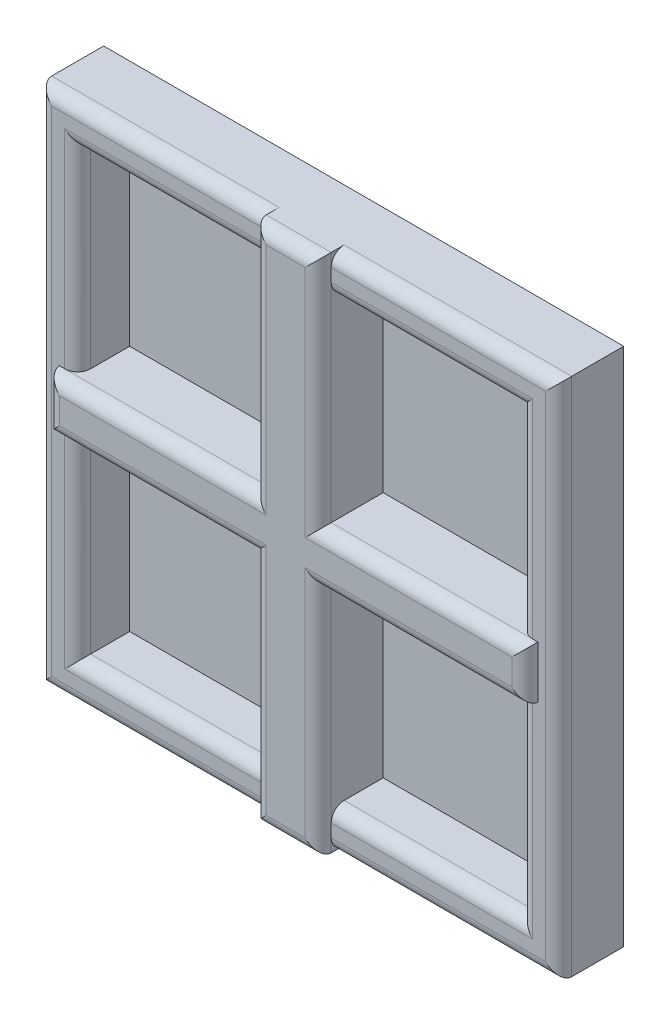
SolidWorks part; units mm, degrees
ref_plane "Front Plane" through (0, 0, 0) normal (0, 0, 1) x (1, 0, 0)
ref_plane "Top Plane" through (0, 0, 0) normal (0, 1, 0) x (1, 0, 0)
ref_plane "Right Plane" through (0, 0, 0) normal (1, 0, 0) x (0, 0, -1)
sketch "Sketch1" plane through (0, 0, 0) normal (0, 0, 1) x (1, 0, 0)
  line L0 (-370, 30) -> (-370, 370)
  line L1 (0, 0) -> (-400, 0)
  line L2 (0, 0) -> (0, 400)
  line L3 (0, 400) -> (-400, 400)
  line L4 (-400, 0) -> (-400, 400)
  line L5 (-30, 370) -> (-370, 370)
  line L6 (-30, 30) -> (-30, 370)
  line L7 (-30, 30) -> (-370, 30)
  dimension "D1" = 400
  dimension "D2" = 400
  dimension "D3" = 30
extrude "Boss-Extrude1" add sketch "Sketch1" along normal blind 50
fillet "Fillet1" radius 10 8 edges at (-200, 370, 50) (-370, 200, 50) (-200, 30, 50) (-30, 200, 50) (-200, 0, 50) (-400, 200, 50) (-200, 400, 50) (0, 200, 50)
sketch "Sketch2" plane through (0, 0, 0) normal (0, 0, 1) x (1, 0, 0)
  line L0 (-200, 400) -> (-200, 0) construction
  line L1 (-400, 400) -> (0, 400) construction
  line L2 (0, 0) -> (-400, 0) construction
  line L3 (0, 200) -> (-400, 200) construction
  line L4 (0, 400) -> (0, 0) construction
  line L5 (-400, 0) -> (-400, 400) construction
  line L6 (0, 400) -> (-400, 400) construction
  line L7 (-225, 400) -> (-175, 400)
  line L8 (-225, 400) -> (-225, 0)
  line L9 (-225, 0) -> (-175, 0)
  line L10 (-175, 400) -> (-175, 0)
  line L11 (-380, 20) -> (-380, 380) construction
  line L12 (-16, 220) -> (-384, 220)
  line L13 (-16, 220) -> (-16, 180)
  line L14 (-16, 180) -> (-384, 180)
  line L15 (-384, 220) -> (-384, 180)
  line L16 (-20, 380) -> (-20, 20) construction
  line L18 (-380, 380) -> (-20, 380)
  line L19 (-380, 380) -> (-380, 20)
  line L20 (-380, 20) -> (-20, 20)
  line L21 (-20, 380) -> (-20, 20)
  dimension "D1" = 4
  dimension "D2" = 4
  dimension "D3" = 4
  dimension "D4" = 40
  dimension "D5" = 50
  dimension "D6" = 4
extrude "Boss-Extrude2" add sketch "Sketch2" along normal blind 60 contours L10 L9 L8 L7 | L12 L15 L14 L13
fillet "Fillet2" radius 10 12 edges at (-200, 0, 60) (-225, 90, 60) (-304.5, 180, 60) (-384, 200, 60) (-304.5, 220, 60) (-225, 310, 60) (-200, 400, 60) (-175, 310, 60) (-95.5, 220, 60) (-16, 200, 60) (-95.5, 180, 60) (-175, 90, 60)
ref_plane "Plane1" through (-225, 380, 50) normal (1, 0, 0) x (0, 0, -1)
sketch "Sketch3" plane through (-225, 380, 50) normal (1, 0, 0) x (0, 0, -1)
sketch "Sketch4" plane through (0, 0, 0) normal (0, 0, 1) x (1, 0, 0)
  line L1 (-380, 380) -> (-20, 380)
  line L2 (-380, 380) -> (-380, 20)
  line L3 (-380, 20) -> (-20, 20)
  line L4 (-20, 380) -> (-20, 20)
extrude "Boss-Extrude3" add sketch "Sketch4" along normal blind 10 separate body
scale "Scale1" bodies to scale 102 103 scale about origin uniform scaling yes scale factor 0.25
scale "Scale2" bodies to scale 105 104 scale about origin uniform scaling yes scale factor 0.32
